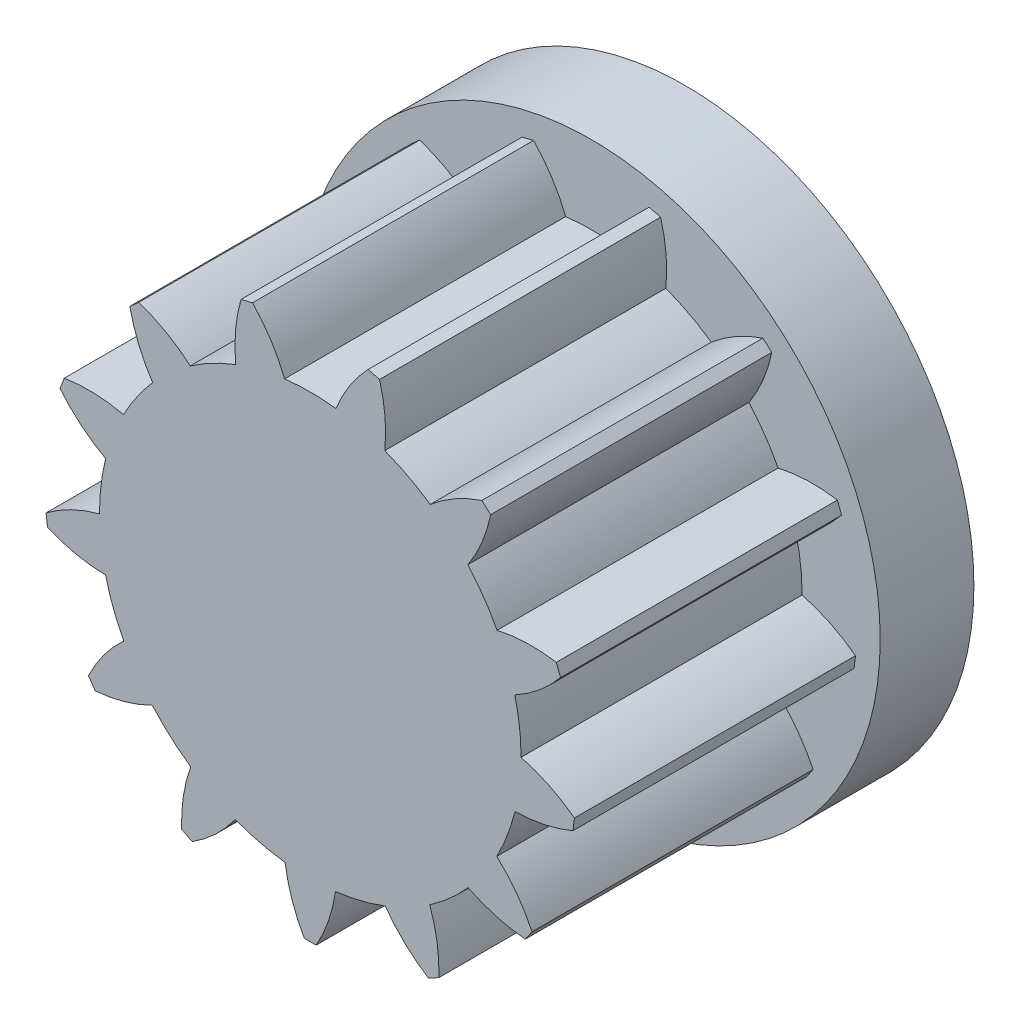
SolidWorks part; units mm, degrees
ref_plane "Front Plane" through (0, 0, 0) normal (0, 0, 1) x (1, 0, 0)
ref_plane "Top Plane" through (0, 0, 0) normal (0, 1, 0) x (1, 0, 0)
ref_plane "Right Plane" through (0, 0, 0) normal (1, 0, 0) x (0, 0, -1)
sketch "Sketch1" plane through (0, 0, 0) normal (0, 0, 1) x (1, 0, 0)
  circle A0 centre (0, 0) radius 9.25
  dimension "D1" = 18.5
extrude "Boss-Extrude1" add sketch "Sketch1" along normal blind 3
sketch "Sketch2" plane through (0, 0, 3) normal (0, 0, 1) x (1, 0, 0)
  line L0 (14.2339, 0) -> (6.75, 0) construction
  line L1 (0, -10.1027) -> (0, -7.2907)
  line L2 (0, 0) -> (2.7187, 11.027) construction
  line L3 (2.2187, 8.2053) -> (1.8498, 8.2963)
  line L4 (5.7778, 6.2344) -> (5.4934, 6.4864)
  line L5 (8.0132, 2.8352) -> (7.8785, 3.1905)
  line L6 (8.4129, -1.2135) -> (8.4588, -0.8363)
  line L7 (6.8853, -4.9842) -> (7.1012, -4.6715)
  line L8 (3.7804, -7.613) -> (4.1169, -7.4365)
  line L9 (-0.1906, -8.4979) -> (0.1894, -8.4979)
  line L10 (-4.1179, -7.4359) -> (-3.7814, -7.6125)
  line L11 (-7.1019, -4.6705) -> (-6.886, -4.9832)
  line L12 (-8.4589, -0.8351) -> (-8.4131, -1.2124)
  line L13 (-7.8781, 3.1916) -> (-8.0128, 2.8363)
  line L14 (-5.4925, 6.4871) -> (-5.7769, 6.2351)
  line L15 (-1.8486, 8.2965) -> (-2.2176, 8.2056)
  line L16 (-6.75, 0) -> (-12.8697, 0) construction
  line L17 (0, 6.75) -> (0, 9.8196)
  arc A0 (-5.4925, 6.4871) -> (-5.7769, 6.2351) centre (0, 0) ccw
  arc A1 (-5.0464, 4.4829) -> (-5.9806, 3.1296) centre (0, 0) ccw
  circle A2 centre (0, 0) radius 7.2907 construction
  circle A3 centre (0, 0) radius 7.7444 construction
  arc A5 (2.3859, 6.3143) -> (2.2187, 8.2053) centre (-2.5478, 6.831) ccw
  arc A6 (0.8227, 6.6997) -> (1.8498, 8.2963) centre (5.4311, 4.8638) cw
  arc A7 (5.047, 4.4822) -> (5.7778, 6.2344) centre (0.9186, 7.2326) ccw
  arc A8 (3.842, 5.5499) -> (5.4934, 6.4864) centre (7.0694, 1.7827) cw
  arc A9 (6.5519, 1.6234) -> (8.0132, 2.8352) centre (4.1745, 5.9772) ccw
  arc A10 (5.9811, 3.1288) -> (7.8785, 3.1905) centre (7.0881, -1.7068) cw
  arc A11 (6.5558, -1.6074) -> (8.4129, -1.2135) centre (6.4741, 3.3526) ccw
  arc A12 (6.75, -0.0091) -> (8.4588, -0.8363) centre (5.483, -4.8053) cw
  arc A13 (5.0579, -4.4699) -> (6.8853, -4.9842) centre (7.2906, -0.0401) ccw
  arc A14 (5.9726, -3.145) -> (7.1012, -4.6715) centre (2.6219, -6.8029) cw
  arc A15 (2.4013, -6.3084) -> (3.7804, -7.613) centre (6.4368, -3.4236) ccw
  arc A16 (3.8269, -5.5603) -> (4.1169, -7.4365) centre (-0.8399, -7.2421) cw
  arc A17 (-0.8054, -6.7018) -> (-0.1906, -8.4979) centre (4.1085, -6.0228) ccw
  arc A18 (0.8046, -6.7019) -> (0.1894, -8.4979) centre (-4.1093, -6.0223) cw
  arc A19 (-3.8277, -5.5598) -> (-4.1179, -7.4359) centre (0.839, -7.2422) ccw
  arc A20 (-2.4021, -6.3081) -> (-3.7814, -7.6125) centre (-6.4373, -3.4228) cw
  arc A21 (-5.973, -3.1442) -> (-7.1019, -4.6705) centre (-2.6228, -6.8026) ccw
  arc A22 (-5.0585, -4.4692) -> (-6.886, -4.9832) centre (-7.2906, -0.0391) cw
  arc A23 (-6.75, -0.0082) -> (-8.4589, -0.8351) centre (-5.4837, -4.8045) ccw
  arc A24 (-6.556, -1.6065) -> (-8.4131, -1.2124) centre (-6.4737, 3.3534) cw
  arc A25 (-5.9806, 3.1296) -> (-7.8781, 3.1916) centre (-7.0883, -1.7058) ccw
  arc A26 (-6.5517, 1.6243) -> (-8.0128, 2.8363) centre (-4.1737, 5.9778) cw
  arc A27 (-3.8412, 5.5505) -> (-5.4925, 6.4871) centre (-7.0691, 1.7837) ccw
  arc A28 (-5.0464, 4.4829) -> (-5.7769, 6.2351) centre (-0.9176, 7.2327) cw
  arc A29 (-0.8218, 6.6998) -> (-1.8486, 8.2965) centre (-5.4305, 4.8646) ccw
  arc A30 (-2.385, 6.3146) -> (-2.2176, 8.2056) centre (2.5487, 6.8307) cw
  arc A31 (-1.8486, 8.2965) -> (-2.2176, 8.2056) centre (0, 0) ccw
  arc A32 (2.2187, 8.2053) -> (0, 8.5) centre (0, 0) ccw
  arc A33 (5.7778, 6.2344) -> (5.4934, 6.4864) centre (0, 0) ccw
  arc A34 (8.0132, 2.8352) -> (7.8785, 3.1905) centre (0, 0) ccw
  arc A35 (8.4129, -1.2135) -> (8.4588, -0.8363) centre (0, 0) ccw
  arc A36 (-7.8781, 3.1916) -> (-8.0128, 2.8363) centre (0, 0) ccw
  arc A37 (-8.4589, -0.8351) -> (-8.4131, -1.2124) centre (0, 0) ccw
  arc A38 (-7.1019, -4.6705) -> (-6.886, -4.9832) centre (0, 0) ccw
  arc A39 (-4.1179, -7.4359) -> (-3.7814, -7.6125) centre (0, 0) ccw
  arc A40 (6.8853, -4.9842) -> (7.1012, -4.6715) centre (0, 0) ccw
  arc A41 (3.7804, -7.613) -> (4.1169, -7.4365) centre (0, 0) ccw
  arc A42 (-0.1906, -8.4979) -> (0.1894, -8.4979) centre (0, 0) ccw
  arc A43 (-2.385, 6.3146) -> (-3.8412, 5.5505) centre (0, 0) ccw
  arc A44 (0.8227, 6.6997) -> (-0.8218, 6.6998) centre (0, 0) ccw
  arc A45 (3.842, 5.5499) -> (2.3859, 6.3143) centre (0, 0) ccw
  arc A46 (5.9811, 3.1288) -> (5.047, 4.4822) centre (0, 0) ccw
  arc A47 (6.75, -0.0091) -> (6.5519, 1.6234) centre (0, 0) ccw
  arc A48 (5.9726, -3.145) -> (6.5558, -1.6074) centre (0, 0) ccw
  arc A49 (3.8269, -5.5603) -> (5.0579, -4.4699) centre (0, 0) ccw
  arc A50 (0.8046, -6.7019) -> (2.4013, -6.3084) centre (0, 0) ccw
  arc A51 (-2.4021, -6.3081) -> (-0.8054, -6.7018) centre (0, 0) ccw
  arc A52 (-5.0585, -4.4692) -> (-3.8277, -5.5598) centre (0, 0) ccw
  arc A53 (-6.556, -1.6065) -> (-5.973, -3.1442) centre (0, 0) ccw
  arc A54 (-6.5517, 1.6243) -> (-6.75, -0.0082) centre (0, 0) ccw
  point P11 (1.8539, 7.5193)
  dimension "D1" = 17
  dimension "D2" = 13.5
  dimension "D5" = 14.5814
  dimension "D6" = 15.4889
  dimension "D3" = 13.85
  dimension "D4" = 0.805
  dimension "D7" = 0.19
  dimension "D8" = 13
extrude "Boss-Extrude2" add sketch "Sketch2" along normal blind 9 contours A26 A54 A23 L12 A24 A53 A21 L11 A22 A52 A19 L10 A20 A51 A17 L9 A18 A50 A15 L8 A16 A49 A13 L7 A14 A48 A11 L6 A12 A47 A9 L5 A10 A46 A7 L4 A8 A45 A5 L3 A6 A44 A29 L15 A30 A43 A27 region at (0, 0, 3)
